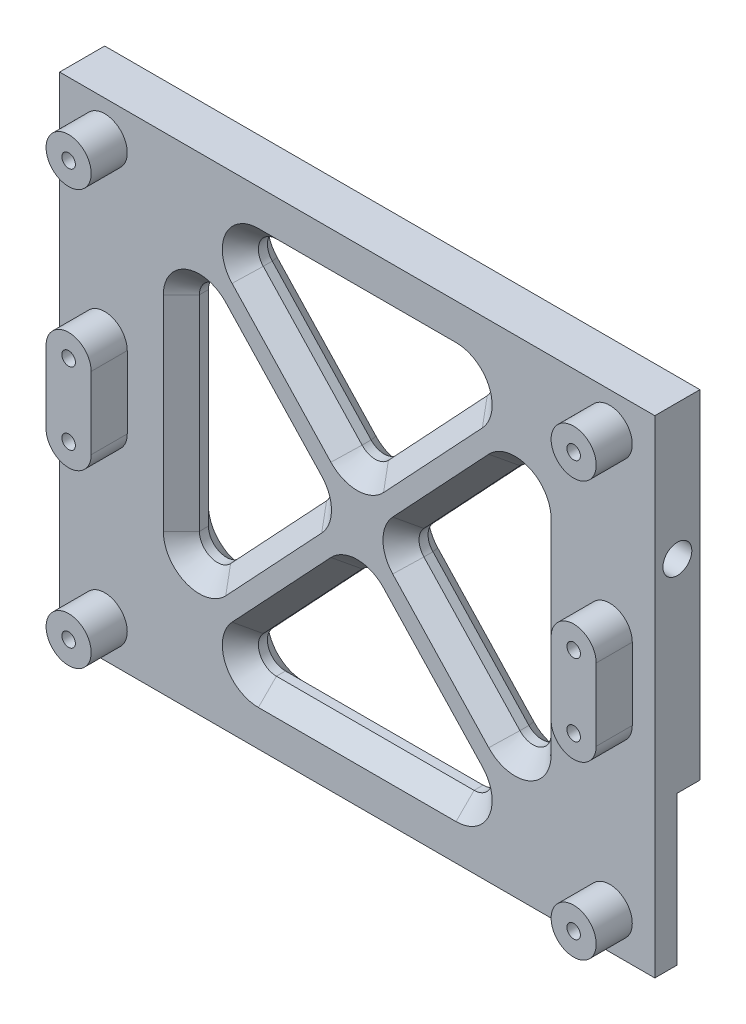
SolidWorks part; units mm, degrees
ref_plane "Ebene vorne" through (0, 0, 0) normal (0, 0, 1) x (1, 0, 0)
ref_plane "Ebene oben" through (0, 0, 0) normal (0, 1, 0) x (1, 0, 0)
ref_plane "Ebene rechts" through (0, 0, 0) normal (1, 0, 0) x (0, 0, -1)
sketch "Sketch1" plane through (0, 0, 0) normal (0, 0, 1) x (1, 0, 0)
  line L1 (33, -27) -> (-33, -27)
  line L2 (33, -27) -> (33, 27)
  line L3 (33, 27) -> (-33, 27)
  line L4 (-33, -27) -> (-33, 27)
  line L5 (33, -27) -> (-33, 27) construction
  line L6 (33, 27) -> (-33, -27) construction
  point P0 (0, 0)
  dimension "D1" = 66
  dimension "D2" = 54
extrude "Boss-Extrude1" add sketch "Sketch1" along normal blind 5
sketch "Sketch2" plane through (0, 0, 5) normal (0, 0, 1) x (1, 0, 0)
  line L0 (0, 27) -> (0, -27) construction
  line L1 (33, 27) -> (-33, 27) construction
  line L2 (-33, -27) -> (33, -27) construction
  line L3 (-33, 0) -> (33, 0) construction
  line L4 (28, -23) -> (-28, -23) construction
  line L5 (28, -23) -> (28, -4) construction
  line L6 (28, -4) -> (-28, -4) construction
  line L7 (-28, -23) -> (-28, -4) construction
  line L8 (28, -23) -> (-28, -4) construction
  line L9 (28, -4) -> (-28, -23) construction
  line L10 (-33, 27) -> (-33, -27) construction
  line L11 (33, -27) -> (33, 27) construction
  line L12 (28, 4) -> (-28, 23) construction
  line L13 (28, 23) -> (-28, 4) construction
  line L14 (-28, 23) -> (-28, 4) construction
  line L15 (28, 4) -> (-28, 4) construction
  line L16 (28, 23) -> (28, 4) construction
  line L17 (28, 23) -> (-28, 23) construction
  line L18 (-25.5, 4) -> (-25.5, -4)
  line L19 (-30.5, 4) -> (-30.5, -4)
  line L20 (25.5, 4) -> (25.5, -4)
  line L21 (30.5, 4) -> (30.5, -4)
  circle A0 centre (-28, -4) radius 0.75
  circle A1 centre (28, -4) radius 0.75
  circle A2 centre (28, -23) radius 0.75
  circle A3 centre (-28, -23) radius 0.75
  arc A4 (-30.5, -4) -> (-25.5, -4) centre (-28, -4) ccw
  arc A5 (25.5, -4) -> (30.5, -4) centre (28, -4) ccw
  circle A6 centre (28, -23) radius 2.5
  circle A7 centre (-28, -23) radius 2.5
  circle A8 centre (-28, 23) radius 2.5
  circle A9 centre (28, 23) radius 2.5
  arc A10 (25.5, 4) -> (30.5, 4) centre (28, 4) cw
  arc A11 (-30.5, 4) -> (-25.5, 4) centre (-28, 4) cw
  circle A12 centre (-28, 23) radius 0.75
  circle A13 centre (28, 23) radius 0.75
  circle A14 centre (28, 4) radius 0.75
  circle A15 centre (-28, 4) radius 0.75
  point P6 (0, -13.5)
  point P37 (0, 13.5)
  dimension "D4" = 1.5
  dimension "D5" = 5
  dimension "D1" = 56
  dimension "D2" = 19
  dimension "D3" = 4
extrude "Boss-Extrude2" add sketch "Sketch2" along normal blind 4
extrude "Cut-Extrude1" cut sketch "Sketch2<2>" against normal blind 4 contours A12 | A13 | A14 | A1 | A2 | A3 | A15 | A0 region at (-28, -4, 5) region at (28, -4, 5) region at (28, -23, 5) region at (-28, -23, 5) region at (-28, 23, 5) region at (28, 23, 5) region at (28, 4, 5) region at (-28, 4, 5)
sketch "Sketch2<2>" plane through (0, 0, 5) normal (0, 0, 1) x (1, 0, 0) same geometry as "Sketch2"
sketch "Sketch3" plane through (0, 0, 5) normal (0, 0, 1) x (1, 0, 0)
  line L0 (25.5, 4) -> (25.5, -4) construction
  line L1 (22.5, -24) -> (-22.5, -24) construction
  line L2 (22.5, -24) -> (22.5, 24) construction
  line L3 (22.5, 24) -> (-22.5, 24) construction
  line L4 (-22.5, -24) -> (-22.5, 24) construction
  line L5 (22.5, -24) -> (-22.5, 24) construction
  line L6 (22.5, 24) -> (-22.5, -24) construction
  line L7 (33, 27) -> (-33, 27) construction
  line L8 (-33, 0) -> (33, 0) construction
  line L9 (-33, 27) -> (-33, -27) construction
  line L10 (33, -27) -> (33, 27) construction
  line L11 (0, 27) -> (0, -27) construction
  line L12 (-33, -27) -> (33, -27) construction
  line L13 (-16.0409, 12.724) -> (-5.3946, 1.3679)
  line L14 (-5.3946, -1.3679) -> (-16.0409, -12.724)
  line L15 (-19.5, -11.3561) -> (-19.5, 11.3561)
  line L16 (-10.9588, 21) -> (10.9588, 21)
  line L17 (12.4179, 17.6321) -> (1.4591, 5.9427)
  line L18 (-1.4591, 5.9427) -> (-12.4179, 17.6321)
  line L19 (5.3946, -1.3679) -> (16.0409, -12.724)
  line L20 (19.5, -11.3561) -> (19.5, 11.3561)
  line L21 (16.0409, 12.724) -> (5.3946, 1.3679)
  line L22 (12.4179, -17.6321) -> (1.4591, -5.9427)
  line L23 (-10.9588, -21) -> (10.9588, -21)
  line L24 (-1.4591, -5.9427) -> (-12.4179, -17.6321)
  arc A0 (12.4179, -17.6321) -> (10.9588, -21) centre (10.9588, -19) cw
  arc A1 (-10.9588, -21) -> (-12.4179, -17.6321) centre (-10.9588, -19) cw
  arc A2 (1.4591, -5.9427) -> (-1.4591, -5.9427) centre (0, -7.3106) ccw
  arc A3 (5.3946, -1.3679) -> (5.3946, 1.3679) centre (6.8537, 0) cw
  arc A4 (16.0409, -12.724) -> (19.5, -11.3561) centre (17.5, -11.3561) ccw
  arc A5 (19.5, 11.3561) -> (16.0409, 12.724) centre (17.5, 11.3561) ccw
  arc A6 (1.4591, 5.9427) -> (-1.4591, 5.9427) centre (0, 7.3106) cw
  arc A7 (10.9588, 21) -> (12.4179, 17.6321) centre (10.9588, 19) cw
  arc A8 (-10.9588, 21) -> (-12.4179, 17.6321) centre (-10.9588, 19) ccw
  arc A9 (-16.0409, -12.724) -> (-19.5, -11.3561) centre (-17.5, -11.3561) cw
  arc A10 (-5.3946, 1.3679) -> (-5.3946, -1.3679) centre (-6.8537, 0) cw
  arc A11 (-16.0409, 12.724) -> (-19.5, 11.3561) centre (-17.5, 11.3561) ccw
  point P0 (0, 0)
  point P34 (15.5753, -21)
  point P37 (-15.5753, -21)
  point P40 (0, -4.3863)
  point P43 (4.1122, 0)
  point P46 (19.5, -16.4137)
  point P49 (19.5, 16.4137)
  point P52 (0, 4.3863)
  point P55 (15.5753, 21)
  point P58 (-15.5753, 21)
  point P61 (-19.5, -16.4137)
  point P64 (-4.1122, 0)
  point P67 (-19.5, 16.4137)
  dimension "D7" = 2
  dimension "D1" = 3
  dimension "D2" = 3
  dimension "D3" = 3
  dimension "D4" = 3
  dimension "D5" = 3
  dimension "D6" = 3
extrude "Cut-Extrude2" cut sketch "Sketch3" against normal blind 14
sketch "Sketch4" plane through (0, -27, 0) normal (0, -1, 0) x (1, 0, 0)
  line L0 (-33, 2.5) -> (33, 2.5) construction
  line L1 (-33, 5) -> (-33, 0) construction
  line L2 (33, 5) -> (33, 0) construction
  circle A0 centre (-13, 2.5) radius 1.6
  circle A1 centre (18, 2.5) radius 0.75
  point P10 (0, 2.5)
  dimension "D1" = 1.5
  dimension "D4" = 3.2
  dimension "D2" = 18
  dimension "D3" = 46
extrude "Cut-Extrude3" cut sketch "Sketch4" against normal blind 5
chamfer "Chamfer1" distance 2 angle 45 48 edges at (18.2355, 13.216, 0) (10.7178, 7.0459, 0) (19.5, 0, 0) (4.8537, 0, 0) (18.2355, -13.216, 0) (10.7178, -7.0459, 0) (0, -5.3106, 0) (-6.9385, -11.7874, 0) (6.9385, -11.7874, 0) (-12.794, -19.7951, 0) (12.794, -19.7951, 0) (0, -21, 0) (-18.2355, -13.216, 0) (-10.7178, -7.0459, 0) (-19.5, 0, 0) (-4.8537, 0, 0) (-18.2355, 13.216, 0) (-10.7178, 7.0459, 0) (-12.794, 19.7951, 0) (-6.9385, 11.7874, 0) (0, 21, 0) (0, 5.3106, 0) (12.794, 19.7951, 0) (6.9385, 11.7874, 0) (0, 21, 5) (-12.794, 19.7951, 5) (12.794, 19.7951, 5) (-6.9385, 11.7874, 5) (6.9385, 11.7874, 5) (0, 5.3106, 5) (18.2355, 13.216, 5) (10.7178, 7.0459, 5) (19.5, 0, 5) (4.8537, 0, 5) (18.2355, -13.216, 5) (10.7178, -7.0459, 5) (0, -5.3106, 5) (-6.9385, -11.7874, 5) (6.9385, -11.7874, 5) (-12.794, -19.7951, 5) (12.794, -19.7951, 5) (0, -21, 5) (-18.2355, 13.216, 5) (-19.5, 0, 5) (-10.7178, 7.0459, 5) (-18.2355, -13.216, 5) (-4.8537, 0, 5) (-10.7178, -7.0459, 5)
sketch "Sketch5" plane through (-33, 0, 0) normal (-1, 0, 0) x (0, 0, 1)
  line L0 (2.5, 27) -> (2.5, -27) construction
  line L1 (5, 27) -> (0, 27) construction
  line L2 (5, -27) -> (0, -27) construction
  circle A0 centre (2.5, 12) radius 1.6
  circle A1 centre (2.5, -18) radius 0.75
  point P10 (2.5, 0)
  dimension "D1" = 1.5
  dimension "D4" = 3.2
  dimension "D2" = 18
  dimension "D3" = 15
extrude "Cut-Extrude4" cut sketch "Sketch5" along normal blind 10 from surface contours A0 starting at face at (33, 0, 2.5)
sketch "Sketch6" plane through (0, 0, 0) normal (0, 0, -1) x (-1, 0, 0)
  line L1 (-33, -27) -> (-23.4, -27)
  line L2 (-33, -27) -> (-33, -10.5)
  line L3 (-33, -10.5) -> (-23.4, -10.5)
  line L4 (-23.4, -27) -> (-23.4, -10.5)
  dimension "D1" = 16.5
  dimension "D2" = 9.6
extrude "Cut-Extrude5" cut sketch "Sketch6" against normal blind 2.54
